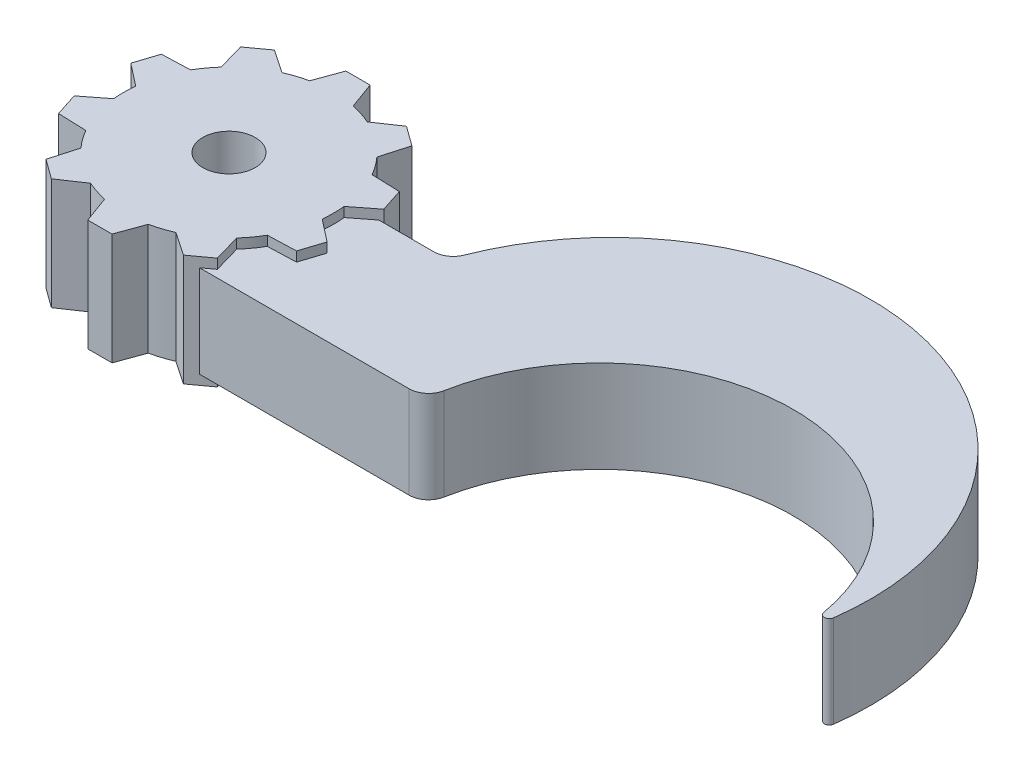
SolidWorks part; units mm, degrees
ref_plane "Front Plane" through (0, 0, 0) normal (0, 0, 1) x (1, 0, 0)
ref_plane "Top Plane" through (0, 0, 0) normal (0, 1, 0) x (1, 0, 0)
ref_plane "Right Plane" through (0, 0, 0) normal (1, 0, 0) x (0, 0, -1)
sketch "Sketch1" plane through (0, 0, 0) normal (0, 1, 0) x (1, 0, 0)
  line L0 (-1.25, 13.3) -> (1.25, 13.3)
  line L1 (-1.25, 13.3) -> (-2.2459, 10.5639)
  line L2 (1.25, 13.3) -> (2.2459, 10.5639)
  line L3 (0, 13.3) -> (0, 0) construction
  line L4 (8.8288, 10.0252) -> (8.0262, 7.2263)
  line L5 (6.8063, 11.4947) -> (8.8288, 10.0252)
  line L6 (6.8063, 11.4947) -> (4.3924, 9.8665)
  line L7 (13.0353, 2.9211) -> (10.7409, 1.1285)
  line L8 (12.2628, 5.2987) -> (13.0353, 2.9211)
  line L9 (12.2628, 5.2987) -> (9.3529, 5.4004)
  line L10 (12.2628, -5.2987) -> (9.3529, -5.4004)
  line L11 (13.0353, -2.9211) -> (12.2628, -5.2987)
  line L12 (13.0353, -2.9211) -> (10.7409, -1.1285)
  line L13 (6.8063, -11.4947) -> (4.3924, -9.8665)
  line L14 (8.8288, -10.0252) -> (6.8063, -11.4947)
  line L15 (8.8288, -10.0252) -> (8.0262, -7.2263)
  line L16 (-1.25, -13.3) -> (-2.2459, -10.5639)
  line L17 (1.25, -13.3) -> (-1.25, -13.3)
  line L18 (1.25, -13.3) -> (2.2459, -10.5639)
  line L19 (-8.8288, -10.0252) -> (-8.0262, -7.2263)
  line L20 (-6.8063, -11.4947) -> (-8.8288, -10.0252)
  line L21 (-6.8063, -11.4947) -> (-4.3924, -9.8665)
  line L22 (-13.0353, -2.9211) -> (-10.7409, -1.1285)
  line L23 (-12.2628, -5.2987) -> (-13.0353, -2.9211)
  line L24 (-12.2628, -5.2987) -> (-9.3529, -5.4004)
  line L25 (-12.2628, 5.2987) -> (-9.3529, 5.4004)
  line L26 (-13.0353, 2.9211) -> (-12.2628, 5.2987)
  line L27 (-13.0353, 2.9211) -> (-10.7409, 1.1285)
  line L28 (-6.8063, 11.4947) -> (-4.3924, 9.8665)
  line L29 (-8.8288, 10.0252) -> (-6.8063, 11.4947)
  line L30 (0, -10.8) -> (29.3692, -10.8)
  line L31 (10.4571, 2.7) -> (0, 2.7) construction
  line L32 (-8.8288, 10.0252) -> (-8.0262, 7.2263)
  line L33 (0, 0) -> (71.2892, 0) construction
  line L34 (10.4571, 2.7) -> (18.4125, 2.7)
  circle A0 centre (0, 0) radius 10.8
  arc A3 (31.3351, -9.1675) -> (29.3692, -10.8) centre (29.3692, -8.8) cw
  arc A4 (18.4125, 2.7) -> (20.2746, 3.97) centre (18.4125, 4.7) ccw
  arc A5 (71.6829, -9.3749) -> (20.2746, 3.97) centre (45.1766, -5.7924) ccw
  arc A6 (70.6949, -9.3941) -> (31.3351, -9.1675) centre (50.9945, -12.8429) ccw
  arc A7 (70.6949, -9.3941) -> (71.6829, -9.3749) centre (71.1874, -9.3079) ccw
  circle A8 centre (0, 0) radius 2.7
  point P48 (0, 0)
  point P61 (0, 0)
  point P62 (0, 0)
  dimension "D3" = 2
  dimension "D4" = 0.5
  dimension "D5" = 5.4
  dimension "D8" = 29.3692
  dimension "D9" = 20
  dimension "D10" = 26.7473
  dimension "D1" = 2.5
  dimension "D2" = 40
  dimension "D6" = 10
  dimension "D7" = 18.4125
  dimension "D11" = 10.8
  dimension "D12" = 5.7924
  dimension "D13" = 12.8429
  dimension "D14" = 0.9959
  dimension "D15" = 0.9959
extrude "Boss-Extrude1" add sketch "Sketch1" along normal blind 11.5 contours A0 A8 | A0 L28 L29 L32 | A0 L25 L26 L27 | A0 L22 L23 L24 | A0 L19 L20 L21 | A0 L16 L17 L18 L30 | A0 L13 L30 L14 L15 | L30 L13 L14 | A0 L10 L11 L12 | A0 L34 L7 L8 L9 | A0 L7 L34 | A0 L2 L0 L1 | A0 L4 L5 L6 | A0 L30 L18 region at (0, 0, -11.8935) region at (0, 0, -10.4945) region at (-6.9908, 0, -9.6221) region at (6.9908, 0, -9.6221) region at (-11.3114, 0, -3.6753) region at (11.307, 0, -4.0491) region at (11.3293, 0, -2.1808) region at (-11.3114, 0, 3.6753) region at (-6.9908, 0, 9.6221) region at (11.3114, 0, 3.6753) region at (-0.0315, 0, 11.9157) region at (7.0085, 0, 9.503) region at (1.6531, 0, 10.7298) region at (6.7817, 0, 11.0316)
extrude "Boss-Extrude3" add sketch "Sketch1<4>" along normal blind 9.5 from offset 1 contours A0 L34 L2 | A6 A7 A5 A4 L34 A0 A3 region at (11.3293, 0, -2.1808) region at (38.21, 0, -5.5761)
sketch "Sketch1<4>" plane through (0, 0, 0) normal (0, 1, 0) x (1, 0, 0) same geometry as "Sketch1"
sketch "Sketch2" plane through (0, 0, 0) normal (1, 0, 0) x (0, 0, -1)
  line L0 (0, -7.0058) -> (0, 13.7554) construction
